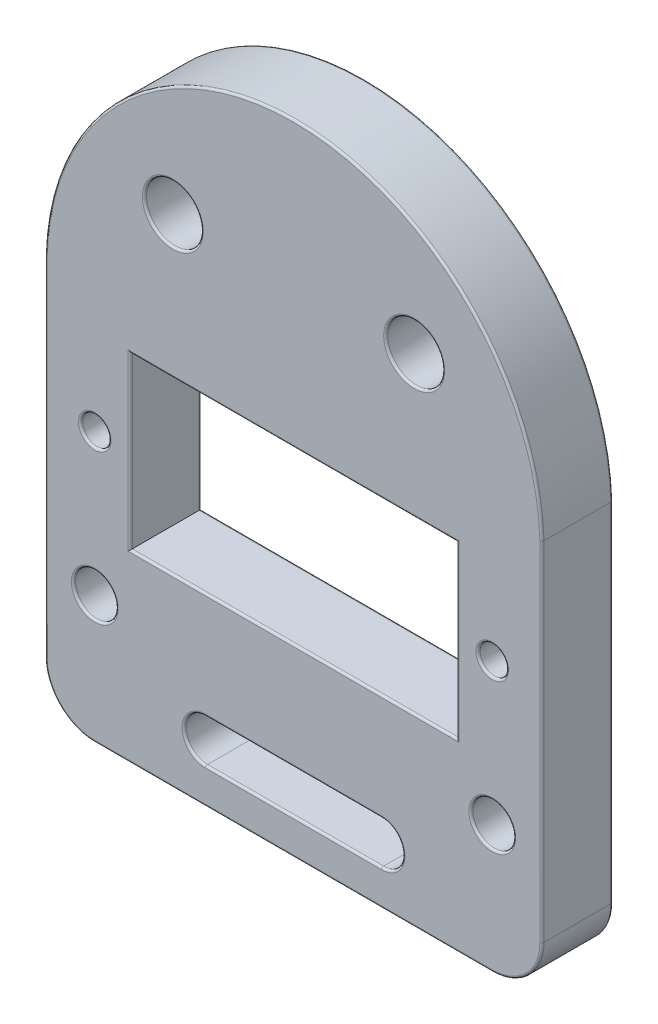
SolidWorks part; units mm, degrees
ref_plane "Płaszczyzna przednia" through (0, 0, 0) normal (0, 0, 1) x (1, 0, 0)
ref_plane "Płaszczyzna górna" through (0, 0, 0) normal (0, 1, 0) x (1, 0, 0)
ref_plane "Płaszczyzna prawa" through (0, 0, 0) normal (1, 0, 0) x (0, 0, -1)
sketch "Szkic1" plane through (0, 0, 0) normal (0, 0, 1) x (1, 0, 0)
  line L0 (0, -19) -> (0, 26) construction
  line L1 (-11.5, -6) -> (11.5, -6)
  line L2 (-11.5, -6) -> (-11.5, 6)
  line L3 (-11.5, 6) -> (11.5, 6)
  line L4 (11.5, -6) -> (11.5, 6)
  line L5 (-11.5, -6) -> (11.5, 6) construction
  line L6 (-11.5, 6) -> (11.5, -6) construction
  line L7 (-6.2, -15) -> (6.2, -15) construction
  line L8 (-6.2, -13.5) -> (6.2, -13.5)
  line L9 (-6.2, -16.5) -> (6.2, -16.5)
  line L11 (-17.5, 9) -> (17.5, 9) construction
  line L12 (-17.5, 9) -> (-17.5, -19)
  line L13 (-17.5, -19) -> (17.5, -19)
  line L14 (17.5, 9) -> (17.5, -19)
  circle A0 centre (-14, 0) radius 1
  circle A1 centre (-14, -10) radius 1.5
  arc A2 (-6.2, -13.5) -> (-6.2, -16.5) centre (-6.2, -15) ccw
  arc A3 (6.2, -16.5) -> (6.2, -13.5) centre (6.2, -15) ccw
  circle A4 centre (-8.5, 16) radius 2
  circle A5 centre (14, -10) radius 1.5
  circle A6 centre (14, 0) radius 1
  circle A7 centre (8.5, 16) radius 2
  arc A8 (-17.5, 9) -> (17.5, 9) centre (0, 8.4926) cw
  point P0 (0, 0)
  point P13 (0, -15)
  dimension "D5" = 2
  dimension "D7" = 3
  dimension "D11" = 1.5
  dimension "D12" = 4
  dimension "D1" = 23
  dimension "D2" = 12
  dimension "D3" = 45
  dimension "D4" = 13
  dimension "D6" = 2.5
  dimension "D8" = 10
  dimension "D9" = 12.4
  dimension "D10" = 4
  dimension "D13" = 8.5
  dimension "D14" = 10
  dimension "D15" = 28
  dimension "D16" = 35
extrude "Dodanie-wyciągnięcie1" add sketch "Szkic1" along normal blind 5
fillet "Zaokrąglenie1" radius 3.5 2 edges at (-17.5, -19, 2.5) (17.5, -19, 2.5)
fillet "Zaokrąglenie2" radius 0.15 40 edges at (6.5, 16, 0) (12.5, -10, 0) (7.7, -15, 0) (0, -16.5, 0) (-7.7, -15, 0) (0, -13.5, 0) (-12.5, -10, 0) (-11.5, 0, 0) (0, 6, 0) (11.5, 0, 0) (0, -6, 0) (16.4749, -17.9749, 0) (17.5, -3.25, 0) (0, 26, 0) (-17.5, -3.25, 0) (-16.4749, -17.9749, 0) (0, -19, 0) (-13, 0, 0) (-6.5, 16, 0) (13, 0, 0) (6.5, 16, 5) (13, 0, 5) (12.5, -10, 5) (-6.5, 16, 5) (0, -16.5, 5) (7.7, -15, 5) (0, -13.5, 5) (-7.7, -15, 5) (0, 26, 5) (17.5, -3.25, 5) (16.4749, -17.9749, 5) (0, -19, 5) (-16.4749, -17.9749, 5) (-17.5, -3.25, 5) (0, 6, 5) (-11.5, 0, 5) (0, -6, 5) (11.5, 0, 5) (-13, 0, 5) (-12.5, -10, 5)
